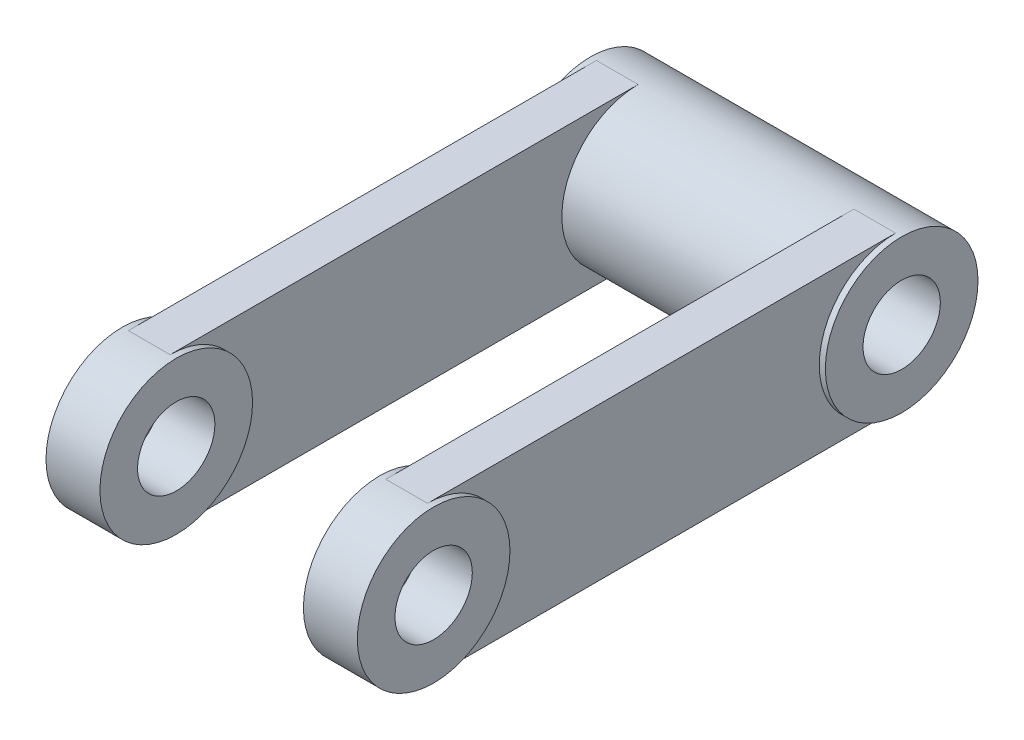
SolidWorks part; units mm, degrees
ref_plane "Front Plane" through (0, 0, 0) normal (0, 0, 1) x (1, 0, 0)
ref_plane "Top Plane" through (0, 0, 0) normal (0, 1, 0) x (1, 0, 0)
ref_plane "Right Plane" through (0, 0, 0) normal (1, 0, 0) x (0, 0, -1)
sketch "Sketch2" plane through (0, 0, 0) normal (1, 0, 0) x (0, 0, -1)
  line L0 (0, 0) -> (460, 0) construction
  line L1 (0, 75) -> (460, 75)
  line L2 (0, -75) -> (460, -75)
  circle A4 centre (0, 0) radius 38
  circle A5 centre (0, 0) radius 75
  circle A6 centre (460, 0) radius 38
  circle A7 centre (460, 0) radius 75
  dimension "D1" = 150
  dimension "D2" = 76
  dimension "D3" = 460
extrude "Boss-Extrude2" add sketch "Sketch2" along normal blind 53 from offset 100 contours A4 A5 | A7 A6 region at (0, 51.533, -51.533) region at (0, 51.533, -511.533)
extrude "Boss-Extrude3" add sketch "Sketch2<5>" along normal blind 41 from offset 106 contours A5 L0 A7 L1 | L0 A5 L2 A7 region at (0, 39.4517, -230) region at (0, -39.4517, -230)
sketch "Sketch2<5>" plane through (0, 0, 0) normal (1, 0, 0) x (0, 0, -1) same geometry as "Sketch2"
extrude "Boss-Extrude4" add sketch "Sketch2<6>" along normal up to surface (100 mm away) contours A7 A6 region at (0, 51.533, -511.533) up to face at (100, 0, -498)
sketch "Sketch2<6>" plane through (0, 0, 0) normal (1, 0, 0) x (0, 0, -1) same geometry as "Sketch2"
mirror "Mirror1" about plane through (0, 0, 0) normal (1, 0, 0) of "Boss-Extrude2", "Boss-Extrude3", "Boss-Extrude4"
